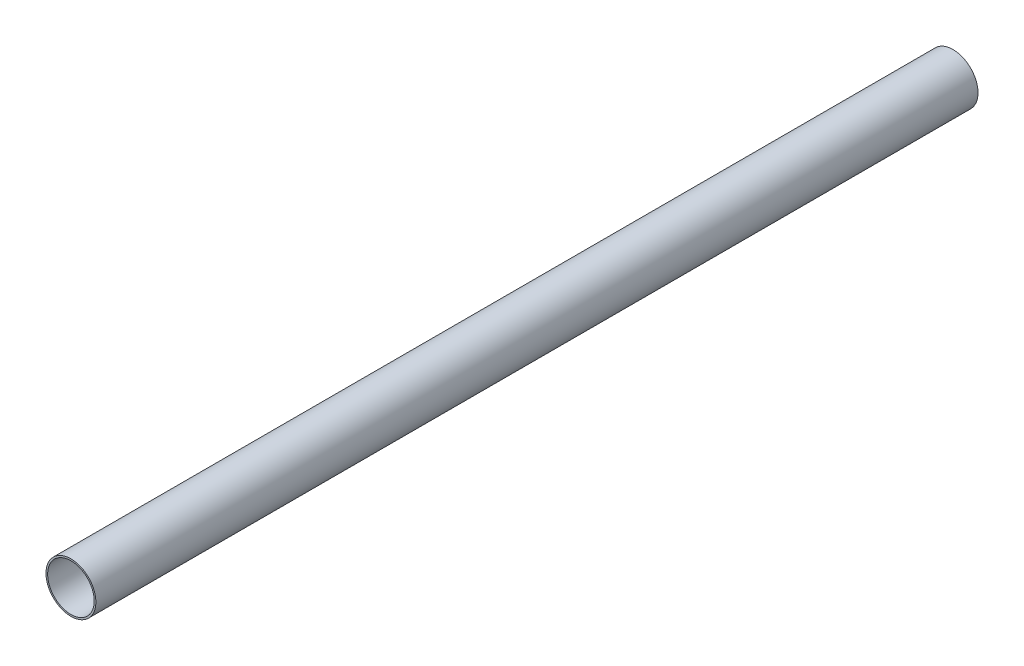
SolidWorks part; units mm, degrees
material "CarbonFiber"
ref_plane "Front Plane" through (0, 0, 0) normal (0, 0, 1) x (1, 0, 0)
ref_plane "Top Plane" through (0, 0, 0) normal (0, 1, 0) x (1, 0, 0)
ref_plane "Right Plane" through (0, 0, 0) normal (1, 0, 0) x (0, 0, -1)
sketch "Эскиз1" plane through (0, 0, 0) normal (0, 0, 1) x (1, 0, 0)
  circle A0 centre (0, 0) radius 15
  circle A1 centre (0, 0) radius 14
  dimension "D1" = 30
  dimension "D2" = 1
extrude "Бобышка-Вытянуть1" add sketch "Эскиз1" along normal mid plane 530
equation "\"DTailTube\"= 16mm'Диаметр трубки хвостового оперения"
equation "\"FusLenght\"= 700mm"
equation "\"DMotor\"= 35.2mm"
equation "\"MotorArm\"= 225mm"
equation "\"DFus\"= 140mm"
equation "\"DFusTube\"= 30mm'Диаметр трубки внутри фюзеляжа"
equation "\"FusTubeHeight\"= 40mm"
equation "\"FusCentralPartLenght\"= 350mm"
equation "\"FusNoseLenght\"= 170mm"
equation "\"WingOffset\"= 1mm'Расстояние от внутренней поверхности фюзеляжа до профиля крыла по вертикали"
equation "\"EllipseRatio\"= 0.95'Центральная часть фюзеляжа - эллипс. Этот параметр - отношение длин осей эллипса"
equation "\"FrameOffset\"= 0.6mm"
equation "\"DThreadedInsert\"= 3.6mm'Внешний диамер резьбовых втулок"
equation "\"CenterSectionLenght\"= 140mm'Длина центроплана"
equation "\"b\"= 1700mm'Размах"
equation "\"cwr\"= 236mm'Корневая хорда крыла"
equation "\"TR\"= 0.75'Сужение крыла"
equation "\"cwt\"= \"TR\" * \"cwr\"'Концевая хорда крыла"
equation "\"DWingMainSpar\"= 16mm'Диаметр главного лонжерона крыла"
equation "\"DWingSecondSpar\"= 8mm'Диаметр второго лонжерона крыла"
equation "\"WingSparsDistance\"= 80mm'Расстояния между отверстиями по лонжерон крыла"
equation "\"c\"= 210mm'САХ крыла"
equation "\"D1@Эскиз1\"=\"DFusTube\""
equation "\"D1@Бобышка-Вытянуть1\"=\"FusTubeLenght\""
equation "\"FusTubeLenght\"= \"FusCentralPartLenght\" + \"FusNoseLenght\" + 10mm'Длина трубки фюзеляжа"
